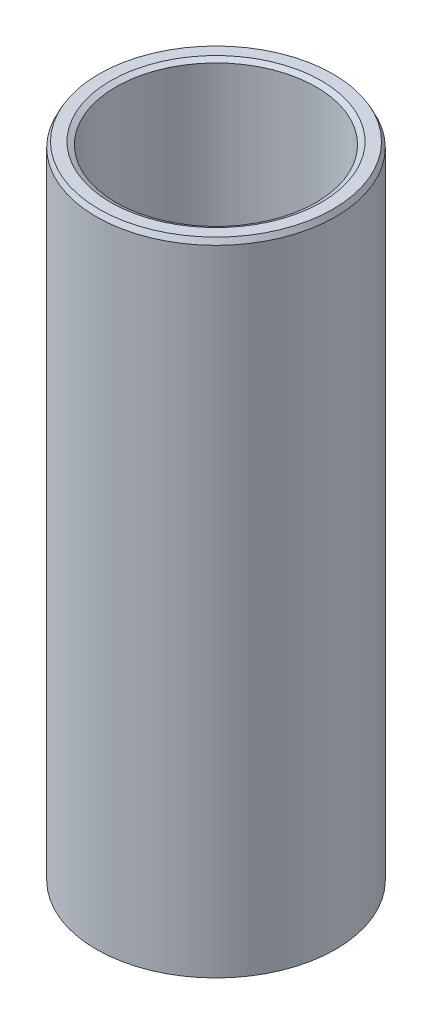
SolidWorks part; units mm, degrees
ref_plane "Front Plane" through (0, 0, 0) normal (0, 0, 1) x (1, 0, 0)
ref_plane "Top Plane" through (0, 0, 0) normal (0, 1, 0) x (1, 0, 0)
ref_plane "Right Plane" through (0, 0, 0) normal (1, 0, 0) x (0, 0, -1)
sketch "Sketch1" plane through (0, 0, 0) normal (0, 1, 0) x (1, 0, 0)
  circle A0 centre (0, 0) radius 55
  dimension "SLEEVE_OD" = 110
extrude "Boss-Extrude1" add sketch "Sketch1" along normal blind 295.0979
sketch "Sketch2" plane through (0, 0, 0) normal (0, 1, 0) x (1, 0, 0)
  circle A0 centre (0, 0) radius 46.0041
  dimension "BORE_D" = 92.0083
extrude "Cut-Extrude1" cut sketch "Sketch2" along normal through all
chamfer "Chamfer1" distance 2.4075 angle 27.096 4 edges at (0, 295.0979, 46.0041) (0, 0, 46.0041) (0, 0, 55) (0, 295.0979, 55) first distance on face at (0, 295.0979, 46.0041) first distance on face at (0, 0, 46.0041) first distance on face at (0, 295.0979, 55)
